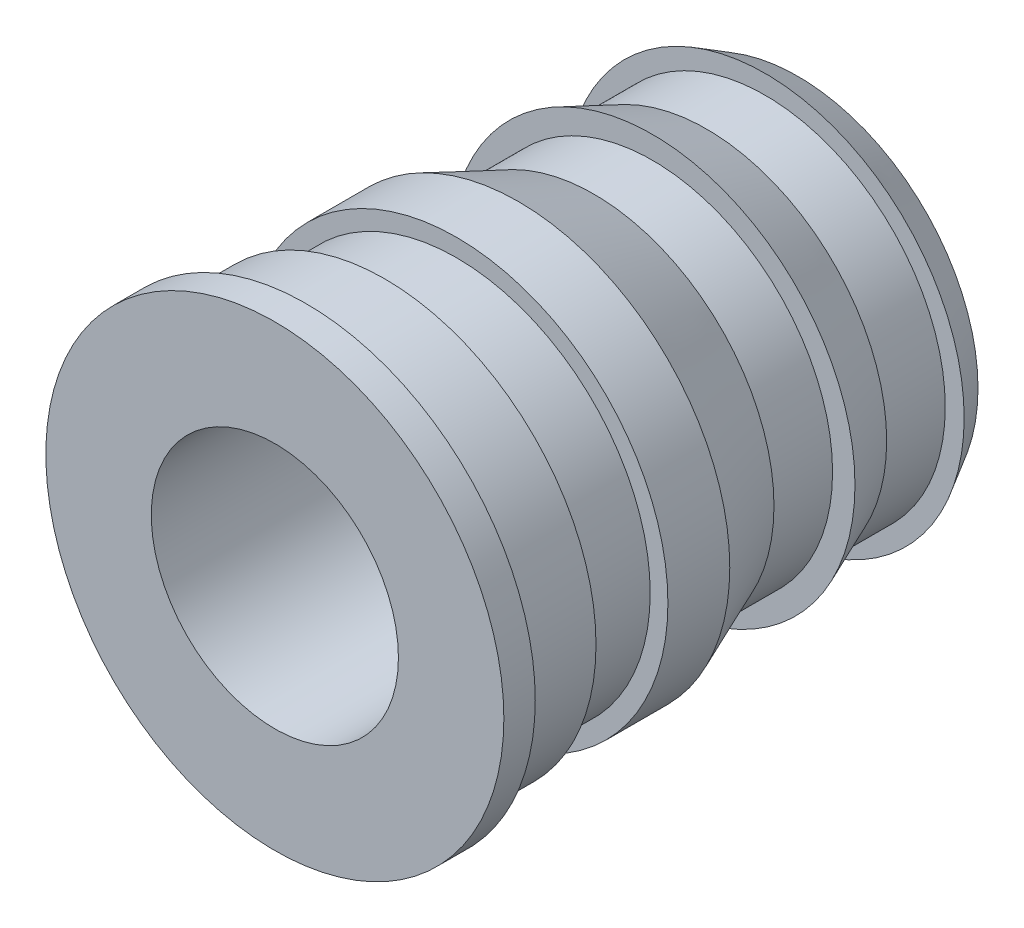
SolidWorks part; units mm, degrees
material "Brass"
ref_plane "Front Plane" through (0, 0, 0) normal (0, 0, 1) x (1, 0, 0)
ref_plane "Top Plane" through (0, 0, 0) normal (0, 1, 0) x (1, 0, 0)
ref_plane "Right Plane" through (0, 0, 0) normal (1, 0, 0) x (0, 0, -1)
sketch "Sketch1" plane through (0, 0, 0) normal (1, 0, 0) x (0, 0, -1)
  line L0 (-3.175, 0) -> (3.175, 0) construction
  line L1 (-3.175, 1.5) -> (-3.175, 2.78)
  line L2 (-3.175, 2.78) -> (-2.794, 2.78)
  line L3 (-2.794, 2.78) -> (-2.794, 2.565)
  line L4 (-2.794, 2.565) -> (-1.8415, 2.565)
  line L5 (-1.8415, 2.565) -> (-1.8415, 2.35)
  line L6 (-1.8415, 2.35) -> (-0.9686, 2.35)
  line L7 (-0.9686, 2.35) -> (-0.9686, 2.565)
  line L9 (-0.2177, 2.565) -> (0.6985, 2.1855)
  line L10 (1.4097, 2.4575) -> (1.4097, 2.1855)
  line L11 (1.4097, 2.1855) -> (0.6985, 2.1855)
  line L12 (1.4097, 2.4575) -> (2.0663, 2.1855)
  line L13 (2.0663, 2.1855) -> (2.7775, 2.1855)
  line L14 (2.7775, 2.1855) -> (2.7775, 2.415)
  line L15 (2.7775, 2.415) -> (3.175, 2.1855)
  line L16 (3.175, 2.1855) -> (3.175, 1.5)
  line L17 (-3.175, 2.415) -> (3.175, 2.415) construction
  line L18 (3.175, 0) -> (3.175, 2.415) construction
  line L19 (-3.175, 0) -> (-3.175, 2.78) construction
  line L20 (-0.9686, 2.565) -> (-0.2177, 2.565)
  line L21 (-3.175, 1.5) -> (3.175, 1.5)
  line L22 (-3.175, -2.415) -> (3.175, -2.415) construction
  line L23 (-3.6438, 1.5541) -> (-3.3938, 1.1211) construction
  line L25 (-3.3938, 1.1211) -> (-3.1438, 1.5541) construction
  line L26 (-3.1438, 1.5541) -> (-3.6438, 1.5541) construction
  line L27 (-3.6125, 1.5) -> (-3.175, 1.5) construction
  line L28 (-3.3938, 1.5541) -> (-3.3938, 1.5) construction
  line L29 (-3.3938, 1.5) -> (-3.3938, 1.1752) construction
  line L30 (-3.3938, 1.1752) -> (-3.3938, 1.1211) construction
  line L31 (-3.425, 1.1752) -> (-3.3625, 1.1752)
  line L32 (-3.6281, 1.5271) -> (-3.1594, 1.5271)
  line L33 (-3.3625, 1.1752) -> (-3.1594, 1.5271)
  line L34 (-3.425, 1.1752) -> (-3.6281, 1.5271)
  line L35 (-3.175, 2.35) -> (3.175, 2.35) construction
  line L36 (-3.175, -2.35) -> (3.175, -2.35) construction
  point P27 (-0.9686, 2.4575)
  point P36 (-3.3938, 1.5271)
  point P41 (0.3014, 2.35)
  dimension "Installed Length" = 6.35
  dimension "Dia A" = 5.56
  dimension "Dia B" = 4.83
  dimension "Thread Dia" = 3
  dimension "D6" = 30
  dimension "D8" = 0.9525
  dimension "D4" = 22.5
  dimension "Thread Pitch" = 0.5
  dimension "D2" = 0.0625
  dimension "Max Hole Dia" = 4.7
  dimension "D3" = 4.371
  dimension "Knurling Length" = 3.4925
  dimension "D1" = 0.381
  dimension "D5" = 1.27
ref_plane "Plane1" through (0, 0, 2.794) normal (0, 0, 1) x (1, 0, 0)
sketch "Sketch2" plane through (0, 0, 2.794) normal (0, 0, 1) x (1, 0, 0)
  line L0 (0, 0) -> (0, 2.565) construction
  line L1 (-0.1789, 2.5588) -> (0, 2.35)
  line L2 (0.1789, 2.5588) -> (0, 2.35)
  line L3 (-0.1789, 2.5588) -> (0, 0) construction
  line L4 (0.1789, 2.5588) -> (0, 0) construction
  line L5 (0, 0) -> (-0.3348, 2.5431) construction
  line L6 (0, 0) -> (0.3348, 2.5431) construction
  line L7 (0, 0) -> (1.8137, 1.8137) construction
  line L8 (0, 0) -> (0, -1.5541) construction
  line L9 (0, 0) -> (0.7771, -1.3459) construction
  circle A0 centre (0, 0) radius 2.35 construction
  circle A1 centre (0, 0) radius 2.565 construction
  arc A2 (-0.1789, 2.5588) -> (0.1789, 2.5588) centre (0, 0) cw
  circle A3 centre (0, 0) radius 1.5541
  dimension "For Hole Taper Angle" = 8
  dimension "Pattern Angle" = 15
  dimension "Helix Angle" = 45
  dimension "D1" = 30
sketch "Sketch3" plane through (0, 0, 0) normal (1, 0, 0) x (0, 0, -1)
  line L0 (-3.175, 1.5) -> (-3.175, 2.78) construction
  line L1 (-3.175, 2.78) -> (-2.794, 2.78) construction
  line L2 (-2.794, 2.78) -> (-2.794, 2.565) construction
  line L3 (-2.794, 2.565) -> (-1.8415, 2.565) construction
  line L4 (-1.8415, 2.565) -> (-1.8415, 2.35) construction
  line L5 (-1.8415, 2.35) -> (-0.9686, 2.35) construction
  line L6 (-0.9686, 2.35) -> (-0.9686, 2.565) construction
  line L8 (-0.2177, 2.565) -> (0.6985, 2.1855) construction
  line L9 (1.4097, 2.1855) -> (0.6985, 2.1855) construction
  line L10 (1.4097, 2.4575) -> (1.4097, 2.1855) construction
  line L11 (1.4097, 2.4575) -> (2.0663, 2.1855) construction
  line L12 (2.0663, 2.1855) -> (2.7775, 2.1855) construction
  line L13 (2.7775, 2.1855) -> (2.7775, 2.415) construction
  line L14 (2.7775, 2.415) -> (3.175, 2.1855) construction
  line L15 (3.175, 2.1855) -> (3.175, 1.5) construction
  line L16 (-3.175, 1.5) -> (3.175, 1.5) construction
  line L17 (-3.175, 1.5) -> (-3.175, 2.78)
  line L18 (-3.175, 2.78) -> (-2.794, 2.78)
  line L19 (-2.794, 2.78) -> (-2.794, 2.565)
  line L20 (-2.794, 2.565) -> (-1.8415, 2.565)
  line L21 (-1.8415, 2.565) -> (-1.8415, 2.35)
  line L22 (-1.8415, 2.35) -> (-0.9686, 2.35)
  line L23 (-0.9686, 2.35) -> (-0.9686, 2.565)
  line L25 (-0.2177, 2.565) -> (0.6985, 2.1855)
  line L26 (1.4097, 2.1855) -> (0.6985, 2.1855)
  line L27 (1.4097, 2.4575) -> (1.4097, 2.1855)
  line L28 (1.4097, 2.4575) -> (2.0663, 2.1855)
  line L29 (2.0663, 2.1855) -> (2.7775, 2.1855)
  line L30 (2.7775, 2.1855) -> (2.7775, 2.415)
  line L31 (2.7775, 2.415) -> (3.175, 2.1855)
  line L32 (3.175, 2.1855) -> (3.175, 1.5)
  line L33 (-3.175, 1.5) -> (3.175, 1.5)
  line L34 (-0.9686, 2.565) -> (-0.2177, 2.565) construction
  line L35 (-0.9686, 2.565) -> (-0.2177, 2.565)
revolve "Revolve1" add sketch "Sketch3" angle 360 about L0
sketch "Sketch4" [suppressed] plane through (0, 0, 2.794) normal (0, 0, 1) x (1, 0, 0)
  circle A2 centre (0, 0) radius 2.565 construction
  circle A3 centre (0, 0) radius 2.565
sketch "Sketch6" [suppressed] plane through (0, 0, 3.175) normal (0, 0, 1) x (1, 0, 0)
  circle A0 centre (0, 0) radius 1.5
curve "Helix/Spiral2" [suppressed] pitch 0.5 height 6.85 turns 13.7
sketch "Sketch7" [suppressed] plane through (0, 0, 0) normal (1, 0, 0) x (0, 0, -1)
  line L0 (-3.425, 1.1752) -> (-3.3625, 1.1752) construction
  line L1 (-3.425, 1.1752) -> (-3.6281, 1.5271) construction
  line L2 (-3.6281, 1.5271) -> (-3.1594, 1.5271) construction
  line L3 (-3.3625, 1.1752) -> (-3.1594, 1.5271) construction
  line L4 (-3.425, 1.1752) -> (-3.3625, 1.1752)
  line L5 (-3.425, 1.1752) -> (-3.6281, 1.5271)
  line L6 (-3.6281, 1.5271) -> (-3.1594, 1.5271)
  line L7 (-3.3625, 1.1752) -> (-3.1594, 1.5271)
sweep "Sweep1" [suppressed] add profiles "Sketch7" path "Helix/Spiral2"
sketch "Sketch8" [suppressed] plane through (0, 0, 3.175) normal (0, 0, 1) x (1, 0, 0)
  circle A0 centre (0, 0) radius 1.5541
extrude "Cut-Extrude1" [suppressed] cut sketch "Sketch8" against normal through all draft 45 and the other way through all
mirror "Mirror1" [suppressed] about plane through (0, 0, 0) normal (0, 0, 1)
curve "Helix/Spiral1" [suppressed] pitch 27.94 height 3.4925 turns 0.125
sketch "Sketch5" [suppressed] plane through (0, 0, 2.794) normal (0, 0, 1) x (1, 0, 0)
  line L0 (-0.1789, 2.5588) -> (0, 2.35) construction
  line L1 (0.1789, 2.5588) -> (0, 2.35) construction
  line L2 (-0.1789, 2.5588) -> (0, 2.35)
  line L3 (0.1789, 2.5588) -> (0, 2.35)
  arc A0 (0.1789, 2.5588) -> (-0.1789, 2.5588) centre (0, 0) ccw construction
  arc A1 (0.1789, 2.5588) -> (-0.1789, 2.5588) centre (0, 0) ccw
sweep "Cut-Sweep1" [suppressed] cut profiles "Sketch5" path "Helix/Spiral1"
pattern_circular "CirPattern1" [suppressed] count 24 over 360 about axis through (0, 0, 3.175) along (0, 0, -1) of bodies 105
equation "\"D8@Sketch1\" = \"Installed Length@Sketch1\" * .15"
equation "\"D4@Helix/Spiral1\"=\"Knurling Length@Sketch1\"*(360/\"Helix Angle@Sketch2\")"
equation "\"D3@Helix/Spiral1\"=\"Knurling Length@Sketch1\""
equation "\"D1@CirPattern1\"=\"D3@CirPattern1\"/\"Pattern Angle@Sketch2\""
equation "\"D2@Sketch1\" = \"Thread Pitch@Sketch1\" / 8"
equation "\"D4@Helix/Spiral2\"=\"Thread Pitch@Sketch1\""
equation "\"D3@Helix/Spiral2\" = \"Installed Length@Sketch1\" + \"Thread Pitch@Sketch1\""
equation "\"D3@Sketch1\"=\"Max Hole Dia@Sketch1\"*.93"
equation "\"Knurling Length@Sketch1\"=\"Installed Length@Sketch1\" * .55"
equation "\"D1@Sketch1\"=\"Installed Length@Sketch1\"*.06"
equation "\"D5@Sketch1\"=\"Installed Length@Sketch1\"*.2"
